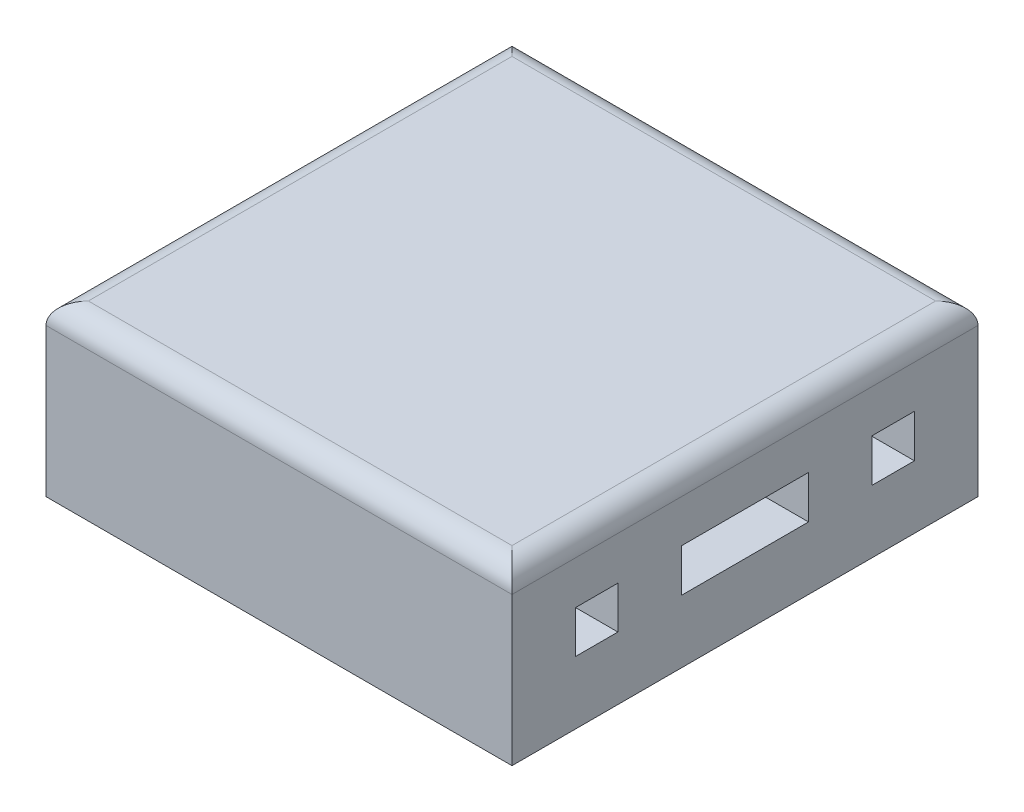
SolidWorks part; units mm, degrees
ref_plane "Front Plane" through (0, 0, 0) normal (0, 0, 1) x (1, 0, 0)
ref_plane "Top Plane" through (0, 0, 0) normal (0, 1, 0) x (1, 0, 0)
ref_plane "Right Plane" through (0, 0, 0) normal (1, 0, 0) x (0, 0, -1)
sketch "Sketch2" plane through (0, 0, 0) normal (0, 1, 0) x (1, 0, 0)
  line L0 (-5.5, -5.5) -> (5.5, -5.5)
  line L1 (0, 0) -> (0, 5.5)
  line L2 (-5.5, -5.5) -> (-5.5, 5.5)
  line L3 (-5.5, 5.5) -> (5.5, 5.5)
  line L4 (5.5, 5.5) -> (5.5, -5.5)
  line L5 (0, 0) -> (-5.5, 0)
  dimension "D1" = 11
  dimension "D2" = 11
  dimension "D3" = 5.5
  dimension "D4" = 5.5
extrude "Boss-Extrude1" add sketch "Sketch2" along normal blind 4 contours L0 L4 L3 L2
sketch "Sketch4" plane through (0, 0, 0) normal (1, 0, 0) x (0, 0, -1)
  line L0 (-4, 1.4828) -> (-4, 2.4828)
  line L1 (-1.5, 2.4957) -> (1.5, 2.4957)
  line L2 (5.5, 4) -> (5.5, 0) construction
  line L3 (-4, 1.4828) -> (-3, 1.4828)
  line L4 (-3, 1.4828) -> (-3, 2.4828)
  line L5 (-3, 2.4828) -> (-4, 2.4828)
  line L6 (-1.5, 1.4828) -> (-1.5, 2.4957)
  line L7 (1.5, 2.4957) -> (1.5, 1.4828)
  line L8 (1.5, 1.4828) -> (-1.5, 1.4828)
  line L9 (-5.5, 4) -> (-5.5, 0) construction
  line L10 (3, 1.4828) -> (3, 2.4957)
  line L11 (3, 2.4957) -> (4, 2.4957)
  line L12 (4, 2.4957) -> (4, 1.4828)
  line L13 (4, 1.4828) -> (3, 1.4828)
  dimension "D1" = 1.5
  dimension "D2" = 1.5
  dimension "D3" = 1.5
  dimension "D4" = 1
  dimension "D5" = 1
  dimension "D6" = 1
  dimension "D7" = 1.5
  dimension "D8" = 3
extrude "Cut-Extrude2" cut sketch "Sketch4" against normal through all both and the other way through all
sketch "Sketch5" plane through (0, 0, 0) normal (0, 1, 0) x (1, 0, 0)
  circle A0 centre (0, 0) radius 2.25
extrude "Cut-Extrude3" cut sketch "Sketch5" against normal through all and the other way blind 2.5
sketch "Sketch8" plane through (0, 0, 0) normal (0, 1, 0) x (1, 0, 0)
  line L0 (0, 0) -> (0, -4)
  line L1 (0, 0) -> (0, 4)
  line L2 (-5.5, -5.5) -> (5.5, -5.5) construction
  line L3 (-5.5, 5.5) -> (5.5, 5.5) construction
  circle A0 centre (0, 4) radius 1
  circle A1 centre (0, -4) radius 1
  dimension "D1" = 2
  dimension "D2" = 2
  dimension "D3" = 1.5
  dimension "D4" = 1.5
extrude "Cut-Extrude4" cut sketch "Sketch8" along normal blind 1 contours A1
extrude "Cut-Extrude5" cut sketch "Sketch8<3>" along normal blind 1 contours A0
sketch "Sketch8<3>" plane through (0, 0, 0) normal (0, 1, 0) x (1, 0, 0) same geometry as "Sketch8"
fillet "Fillet2" radius 0.5 4 edges at (0, 4, 5.5) (-5.5, 4, 0) (0, 4, -5.5) (5.5, 4, 0)
